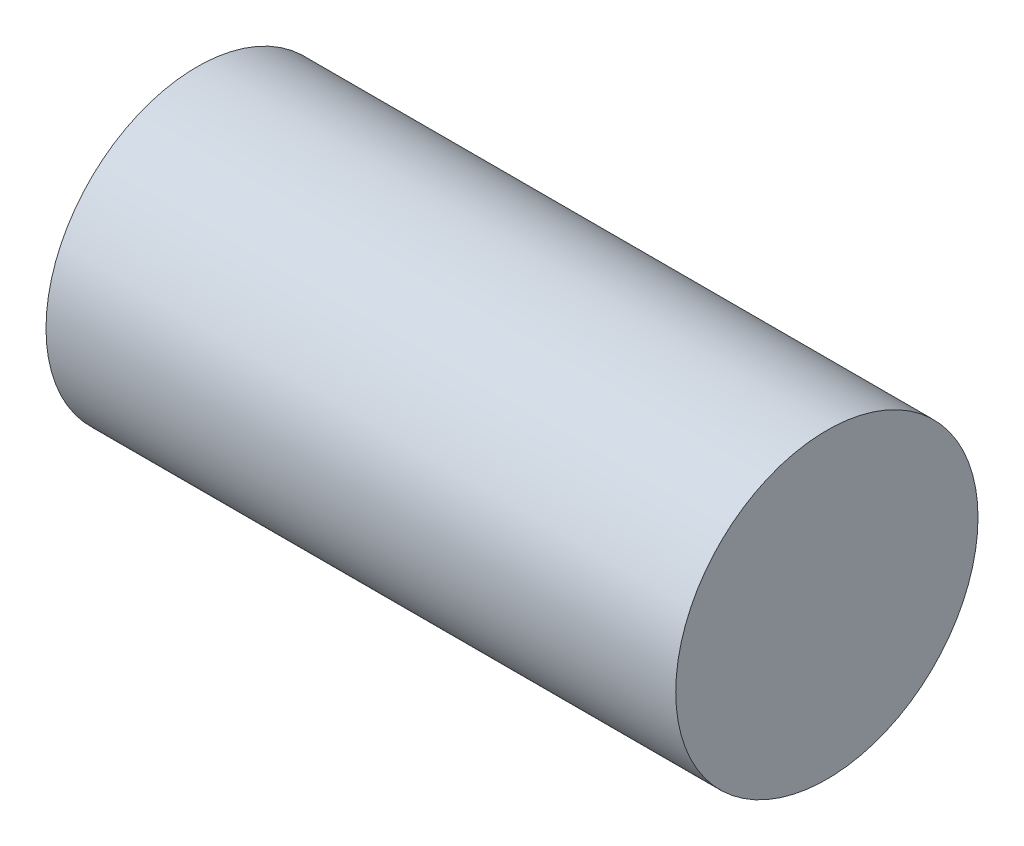
SolidWorks part; units mm, degrees
ref_plane "Front Plane" through (0, 0, 0) normal (0, 0, 1) x (1, 0, 0)
ref_plane "Top Plane" through (0, 0, 0) normal (0, 1, 0) x (1, 0, 0)
ref_plane "Right Plane" through (0, 0, 0) normal (1, 0, 0) x (0, 0, -1)
sketch "Hose_End_8 Sketch" plane through (0, 0, 0) normal (0, 0, 1) x (1, 0, 0)
  line L0 (-1000, 0) -> (1000, 0) construction
  line L1 (0, 0) -> (0, 12)
  line L2 (0, 12) -> (50, 12)
  line L3 (50, 12) -> (50, 0)
  line L4 (50, 0) -> (0, 0)
revolve "Hose_End_8" add sketch "Hose_End_8 Sketch" angle 360 about L0
ref_axis "Engine Axis" through (52.5, 0, 0) along (-1, 0, 0)
sketch "Socket 1 Sketch" plane through (0, 0, 0) normal (0, 0, 1) x (1, 0, 0)
  line L0 (-1000, 0) -> (1000, 0) construction
  line L1 (-1, 0) -> (-1, 6.35)
  line L2 (-1, 6.35) -> (22.9, 6.35)
  line L3 (22.9, 6.35) -> (22.9, 0)
  line L4 (22.9, 0) -> (-1, 0)
revolve "Socket 1" cut sketch "Socket 1 Sketch" angle 360 about L0
